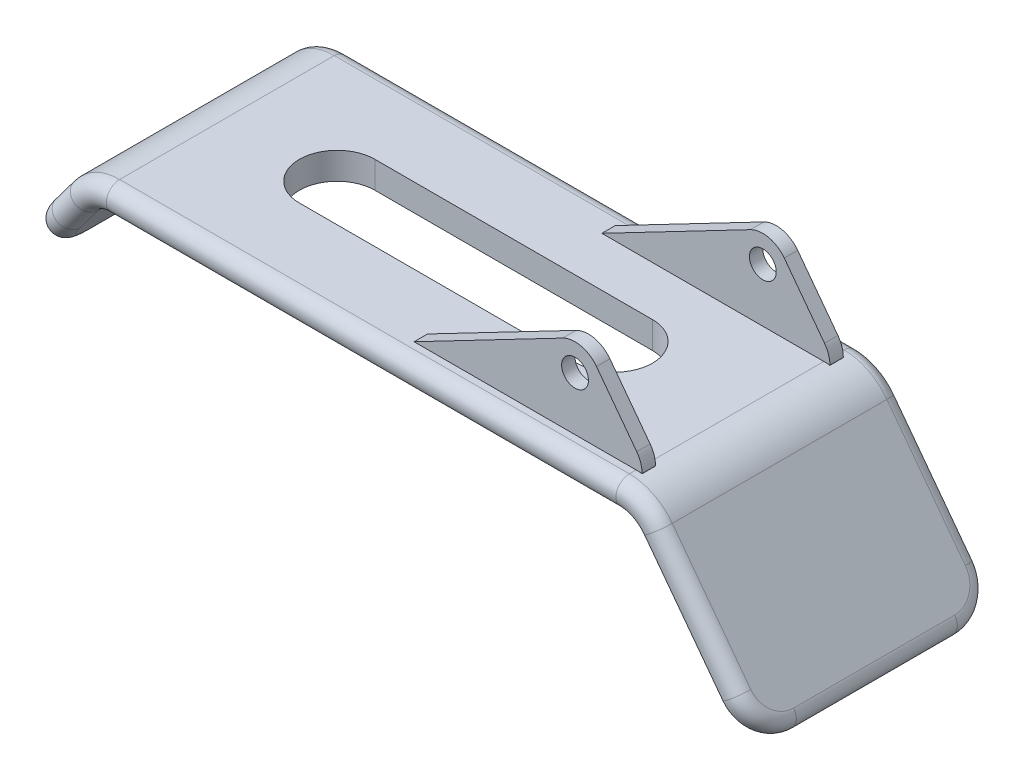
SolidWorks part; units mm, degrees
ref_plane "Front Plane" through (0, 0, 0) normal (0, 0, 1) x (1, 0, 0)
ref_plane "Top Plane" through (0, 0, 0) normal (0, 1, 0) x (1, 0, 0)
ref_plane "Right Plane" through (0, 0, 0) normal (1, 0, 0) x (0, 0, -1)
sketch "Sketch1" plane through (0, 0, 0) normal (0, 0, 1) x (1, 0, 0)
  line L0 (-19, 0) -> (19, 0)
  line L1 (20.6, -0.8) -> (28.25, -11)
  line L2 (-20.6, -0.8) -> (-23.75, -5)
  line L3 (0, 0) -> (0, -11) construction
  line L4 (-28.25, -11) -> (28.25, -11) construction
  line L5 (-23.75, -5) -> (-28.25, -11) construction
  arc A0 (-19, 0) -> (-20.6, -0.8) centre (-19, -2) ccw
  arc A1 (19, 0) -> (20.6, -0.8) centre (19, -2) cw
  point P10 (-20, 0)
  point P13 (20, 0)
  dimension "D5" = 2
  dimension "D1" = 11
  dimension "D2" = 52
  dimension "D3" = 40
  dimension "D4" = 5
extrude "Extrude-Thin1" add sketch "Sketch1" along normal mid plane 18 thin thin type one direction wall 2
fillet "Fillet1" radius 3 4 edges at (-24.55, -4.4, 9) (-24.55, -4.4, -9) (29.05, -10.4, -9) (29.05, -10.4, 9)
fillet "Fillet2" 2 edges at (0, 2, 9) (0, 0, 9) type full round first side face at (0, 2, 0) second side face at (0, 0, 0) middle face at (0.75, -1.3056, 9)
ref_plane "Plane1" through (0, 0, 7.5) normal (0, 0, 1) x (1, 0, 0)
sketch "Sketch2" plane through (0, 0, 7.5) normal (0, 0, 1) x (1, 0, 0)
  line L0 (2.45, 2) -> (13.5255, 7.7735)
  line L1 (-19, 2) -> (19, 2) construction
  line L2 (16.05, 7.2) -> (19.05, 3.2)
  line L3 (19.45, 2) -> (19.45, 1.9746)
  line L4 (2.45, 2) -> (19, 2)
  line L5 (19, 0) -> (-19, 0) construction
  arc A0 (13.5255, 7.7735) -> (16.05, 7.2) centre (14.45, 6) cw
  arc A1 (22.2, 0.4) -> (19, 2) centre (19, -2) ccw construction
  arc A2 (19.05, 3.2) -> (19.45, 2) centre (17.45, 2) cw
  arc A3 (19.45, 1.9746) -> (19, 2) centre (19, -2) ccw
  arc A4 (27.65, -10.2) -> (29.25, -9) centre (28.45, -9.6) ccw construction
  circle A5 centre (14.45, 6) radius 1
  dimension "D1" = 2
  dimension "D4" = 2
  dimension "D7" = 2
  dimension "D2" = 8
  dimension "D3" = 14
  dimension "D5" = 12
  dimension "D6" = 17
extrude "Extrude1" add sketch "Sketch2" against normal blind 1
mirror "Mirror1" about plane through (0, 0, 0) normal (0, 0, 1) of "Extrude1"
sketch "Sketch3" plane through (0, 2, 0) normal (0, 1, 0) x (1, 0, 0)
  line L0 (-10.7859, 0) -> (9.903, 0) construction
  line L1 (-10.7859, 2.8174) -> (9.903, 2.8174)
  line L2 (-10.7859, -2.8174) -> (9.903, -2.8174)
  arc A0 (-10.7859, 2.8174) -> (-10.7859, -2.8174) centre (-10.7859, 0) ccw
  arc A1 (9.903, -2.8174) -> (9.903, 2.8174) centre (9.903, 0) ccw
  point P3 (-0.4414, 0)
extrude "Extrude2" cut sketch "Sketch3" against normal through all
